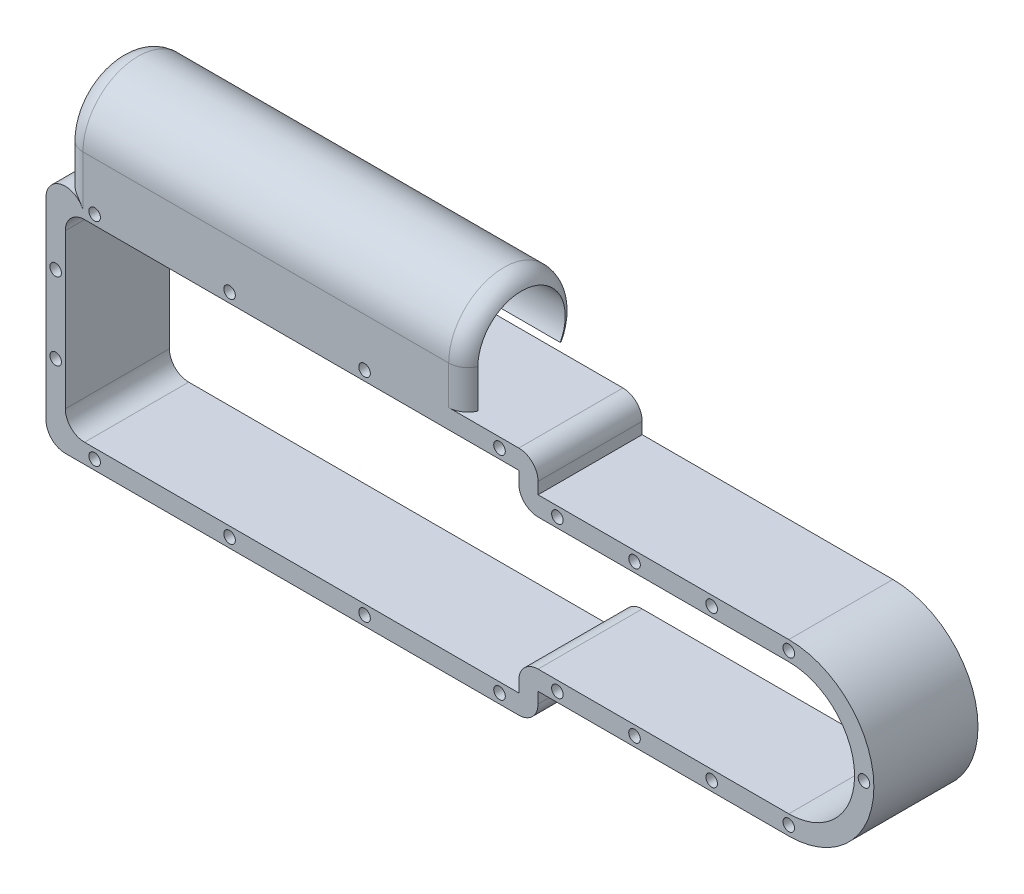
SolidWorks part; units mm, degrees
material "ABS"
ref_plane "Front Plane" through (0, 0, 0) normal (0, 0, 1) x (1, 0, 0)
ref_plane "Top Plane" through (0, 0, 0) normal (0, 1, 0) x (1, 0, 0)
ref_plane "Right Plane" through (0, 0, 0) normal (1, 0, 0) x (0, 0, -1)
sketch "Sketch1" plane through (0, 0, 0) normal (0, 0, 1) x (1, 0, 0)
  line L0 (63.8, 22) -> (128.81, 22)
  line L1 (-58.8, -30) -> (58.8, -30)
  line L2 (-63.8, -25) -> (-63.8, 25)
  line L3 (-58.8, 30) -> (58.8, 30)
  line L4 (63.8, -25) -> (63.8, 25)
  line L5 (-63.8, -30) -> (63.8, 30) construction
  line L6 (-63.8, 30) -> (63.8, -30) construction
  line L7 (63.8, -22.136) -> (128.81, -22.136)
  arc A0 (-63.8, -25) -> (-58.8, -30) centre (-58.8, -25) ccw
  arc A1 (58.8, -30) -> (63.8, -25) centre (58.8, -25) ccw
  arc A2 (63.8, 25) -> (58.8, 30) centre (58.8, 25) ccw
  arc A3 (-58.8, 30) -> (-63.8, 25) centre (-58.8, 25) ccw
  circle A4 centre (128.81, 0) radius 10
  arc A5 (128.81, 22) -> (128.81, -22.136) centre (128.81, -0.068) cw
  point P0 (0, 0)
  dimension "D2" = 5
  dimension "D5" = 20
  dimension "D7" = 22.136
  dimension "D4" = 22
  dimension "D1" = 60
  dimension "D3" = 117.6
  dimension "D6" = 192.61
extrude "Boss-Extrude1" add sketch "Sketch1" along normal blind 27 contours A5 L0 L4 L7 A4 | L3 A3 L2 A0 L1 A1 L4 A2 region at (102.8766, -0.0744, 0) region at (0, 0, 0)
sketch "Sketch2" plane through (0, 0, 27) normal (0, 0, 1) x (1, 0, 0)
  line L8 (-63.8, -25) -> (-63.8, 25) construction
  line L9 (-58.8, 30) -> (58.8, 30) construction
  circle A5 centre (-51.2, 27.5) radius 1.5
  circle A6 centre (-61.3, 10) radius 1.5
  dimension "D3" = 3
  dimension "D6" = 3
  dimension "D4" = 12.6
  dimension "D5" = 2.5
  dimension "D7" = 2.5
  dimension "D8" = 20
sketch "Sketch4" plane through (0, 0, 27) normal (0, 0, 1) x (1, 0, 0)
  line L14 (128.81, 17) -> (58.8, 17)
  line L15 (58.8, 17) -> (58.8, 25)
  line L16 (58.8, 25) -> (-58.8, 25)
  line L17 (-58.8, 25) -> (-58.8, -25)
  line L18 (-58.8, -25) -> (58.8, -25)
  line L19 (58.8, -25) -> (58.8, -17.136)
  line L20 (58.8, -17.136) -> (128.81, -17.136)
  line L21 (128.81, 17) -> (58.8, 17)
  line L22 (58.8, 17) -> (58.8, 25)
  line L23 (58.8, 25) -> (-58.8, 25)
  line L24 (-58.8, 25) -> (-58.8, -25)
  line L25 (-58.8, -25) -> (58.8, -25)
  line L26 (58.8, -25) -> (58.8, -17.136)
  line L27 (58.8, -17.136) -> (128.81, -17.136)
  arc A10 (128.81, -17.136) -> (128.81, 17) centre (128.81, -0.068) ccw
  arc A11 (128.81, -17.136) -> (128.81, 17) centre (128.81, -0.068) ccw
  dimension "D1" = 5
extrude "Cut-Extrude3" cut sketch "Sketch4" against normal through all
extrude "Cut-Extrude4" cut sketch "Sketch2" against normal through all
pattern_linear "LPattern1" count 4 spacing 35 along (1, 0, 0) count 2 spacing 55 along (0, -1, 0) of face at (-49.7, 27.5, 0)
pattern_linear "LPattern2" count 2 spacing 20 along (0, -1, 0) of face at (-59.8, 10, 0)
fillet "Fillet1" radius 5 2 edges at (58.8, -17.136, 13.5) (58.8, 17, 13.5)
fillet "Fillet2" radius 5 2 edges at (-58.8, -25, 13.5) (-58.8, 25, 13.5)
ref_plane "Plane1" through (-58.8, 0, 0) normal (-1, 0, 0) x (0, 0, 1)
sketch "Sketch6" plane through (-58.8, 0, 0) normal (-1, 0, 0) x (0, 0, 1)
  line L6 (27, 30) -> (27, 40)
  line L7 (24, 30) -> (24, 40)
  line L8 (27, 30) -> (24, 30)
  line L9 (0, 33.3438) -> (2.6562, 34.7382)
  arc A2 (27, 40) -> (0, 33.3438) centre (12.6795, 40) ccw
  arc A3 (24, 40) -> (2.6562, 34.7382) centre (12.6795, 40) ccw
  dimension "D1" = 10
  dimension "D2" = 3
extrude "Boss-Extrude2" add sketch "Sketch6" against normal blind 104
fillet "Fillet3" radius 5 2 edges at (-58.8, 35, 27) (-58.8, 53.9042, 9.2518)
fillet "Fillet4" radius 5 2 edges at (45.2, 35, 27) (45.2, 53.9042, 9.2518)
sketch "Sketch8" plane through (0, 0, 27) normal (0, 0, 1) x (1, 0, 0)
  line L1 (-54.2174, 51.0277) -> (-39.2174, 51.0277)
  line L2 (-54.2174, 51.0277) -> (-54.2174, 30)
  line L3 (-54.2174, 30) -> (-39.2174, 30)
  line L4 (-39.2174, 51.0277) -> (-39.2174, 30)
  circle A0 centre (-51.2, 27.5) radius 1.5 construction
  dimension "D1" = 15
  dimension "D2" = 2.5
sketch "Sketch13" plane through (0, 0, 27) normal (0, 0, 1) x (1, 0, 0)
  line L0 (63.8, 22) -> (128.81, 22) construction
  circle A0 centre (68.81, 19.5) radius 1.5
  circle A1 centre (88.81, 19.5) radius 1.5
  arc A2 (128.81, -22.136) -> (128.81, 22) centre (128.81, -0.068) ccw construction
  circle A3 centre (108.81, 19.5) radius 1.5
  circle A4 centre (128.81, 19.5) radius 1.5
  circle A5 centre (88.81, -19.64) radius 1.5
  circle A6 centre (108.81, -19.64) radius 1.5
  circle A7 centre (128.81, -19.64) radius 1.5
  circle A8 centre (68.81, -19.64) radius 1.5
  circle A9 centre (148.31, 0) radius 1.5
  dimension "D1" = 3
  dimension "D6" = 3
  dimension "D8" = 19.5
  dimension "D9" = 20
  dimension "D2" = 2.5
  dimension "D3" = 60
  dimension "D7" = 22
  dimension "D4" = 4
  dimension "D5" = 2
extrude "Cut-Extrude8" cut sketch "Sketch13" against normal through all
